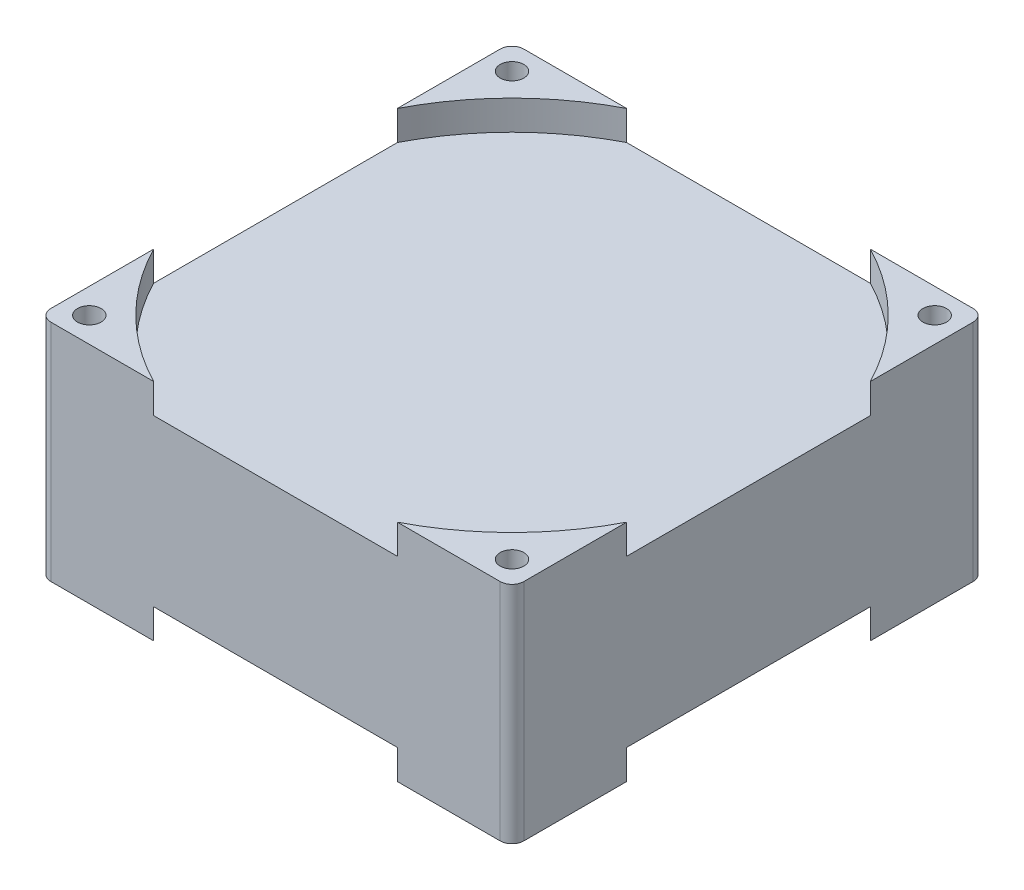
SolidWorks part; units mm, degrees
ref_plane "Front Plane" through (0, 0, 0) normal (0, 0, 1) x (1, 0, 0)
ref_plane "Top Plane" through (0, 0, 0) normal (0, 1, 0) x (1, 0, 0)
ref_plane "Right Plane" through (0, 0, 0) normal (1, 0, 0) x (0, 0, -1)
sketch "Sketch1" plane through (0, 0, 0) normal (0, 1, 0) x (1, 0, 0)
  line L1 (40, -40) -> (-40, -40)
  line L2 (40, -40) -> (40, 40)
  line L3 (40, 40) -> (-40, 40)
  line L4 (-40, -40) -> (-40, 40)
  line L5 (40, -40) -> (-40, 40) construction
  line L6 (40, 40) -> (-40, -40) construction
  point P0 (0, 0)
  dimension "D1" = 80
extrude "Body" add sketch "Sketch1" along normal blind 38 contours L3 L4 L1 L2
sketch "Sketch2" plane through (0, 38, 0) normal (0, 1, 0) x (1, 0, 0)
  line L1 (35.75, -35.75) -> (-35.75, -35.75) construction
  line L2 (35.75, -35.75) -> (35.75, 35.75) construction
  line L3 (35.75, 35.75) -> (-35.75, 35.75) construction
  line L4 (-35.75, -35.75) -> (-35.75, 35.75) construction
  line L5 (35.75, -35.75) -> (-35.75, 35.75) construction
  line L6 (35.75, 35.75) -> (-35.75, -35.75) construction
  circle A0 centre (-35.75, 35.75) radius 2
  circle A1 centre (35.75, 35.75) radius 2
  circle A2 centre (35.75, -35.75) radius 2
  circle A3 centre (-35.75, -35.75) radius 2
  point P2 (27.512, -29.792)
  point P4 (-27.968, -30.324)
  point P6 (0, 0)
  point P8 (0, 0)
  point P9 (27.208, 29.792)
  dimension "D1" = 4
  dimension "D2" = 71.5
extrude "Cut-Extrude1" cut sketch "Sketch2" against normal blind 38
sketch "Sketch3" plane through (0, 38, 0) normal (0, 1, 0) x (1, 0, 0)
  line L0 (-40, 20.6155) -> (-40, -20.6155)
  line L1 (-40, -40) -> (-40, 40) construction
  line L2 (-20.6155, -40) -> (20.6155, -40)
  line L3 (40, -40) -> (-40, -40) construction
  line L4 (40, -20.6155) -> (40, 20.6155)
  line L5 (40, -40) -> (40, 40) construction
  line L6 (20.6155, 40) -> (-20.6155, 40)
  line L7 (40, 40) -> (-40, 40) construction
  arc A0 (-20.6155, 40) -> (-40, 20.6155) centre (0, 0) ccw
  arc A1 (40, 20.6155) -> (20.6155, 40) centre (0, 0) ccw
  arc A2 (20.6155, -40) -> (40, -20.6155) centre (0, 0) ccw
  arc A3 (-40, -20.6155) -> (-20.6155, -40) centre (0, 0) ccw
  point P19 (-20.6155, 40)
  point P20 (20.6155, 40)
  point P21 (40, 20.6155)
  point P22 (40, -20.6155)
  point P23 (19.888, -40)
  point P24 (20.6155, -40)
  point P25 (-20.6155, -40)
  point P26 (-40, -20.6155)
  dimension "D1" = 90
extrude "Cut-Extrude2" cut sketch "Sketch3" against normal blind 5
ref_plane "Plane1" through (0, 19, 0) normal (0, 1, 0) x (1, 0, 0)
mirror "Mirror1" about plane through (0, 19, 0) normal (0, 1, 0) of "Cut-Extrude2"
fillet "Fillet1" radius 2 4 edges at (-40, 19, 40) (40, 19, 40) (40, 19, -40) (-40, 19, -40)
